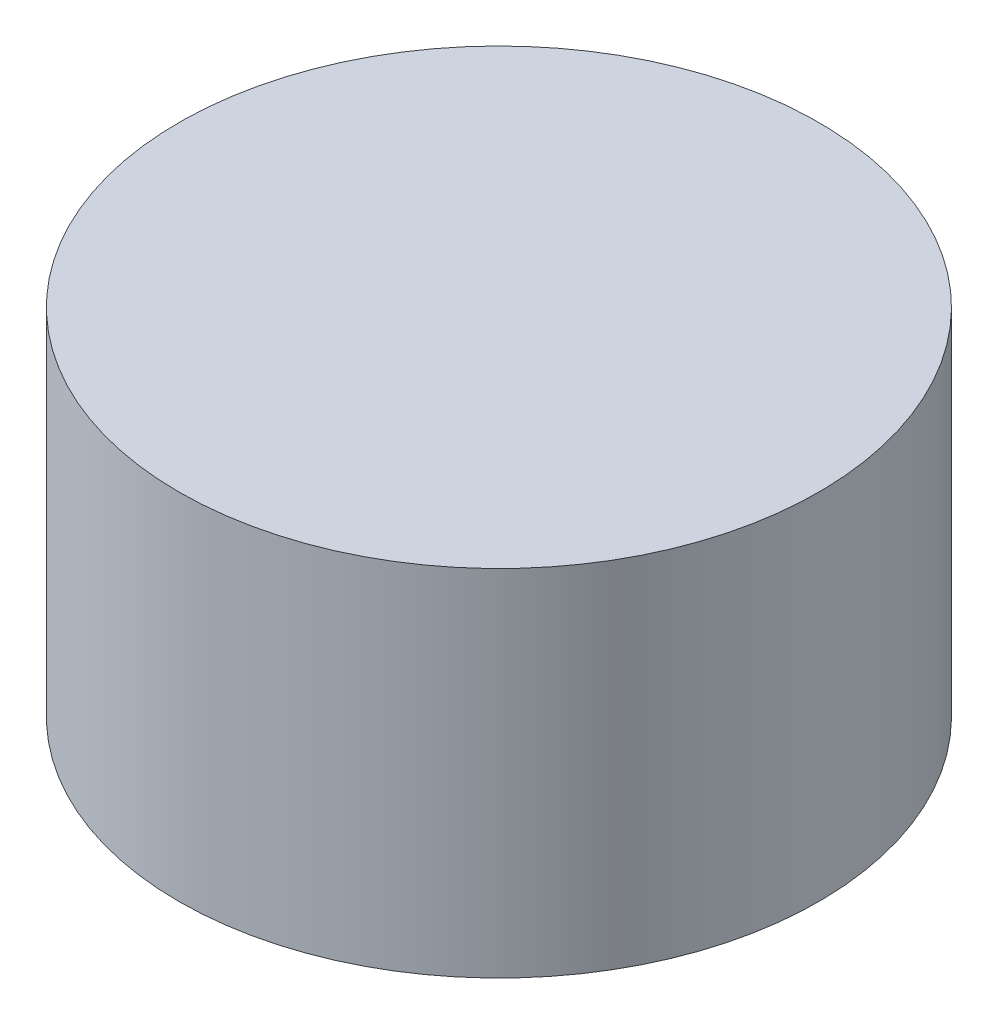
SolidWorks part; units mm, degrees
ref_plane "Front Plane" through (0, 0, 0) normal (0, 0, 1) x (1, 0, 0)
ref_plane "Top Plane" through (0, 0, 0) normal (0, 1, 0) x (1, 0, 0)
ref_plane "Right Plane" through (0, 0, 0) normal (1, 0, 0) x (0, 0, -1)
sketch "Sketch1" plane through (0, 0, 0) normal (0, 1, 0) x (1, 0, 0)
  circle A0 centre (0, 0) radius 64.9649
extrude "Boss-Extrude1" add sketch "Sketch1" along normal blind 72
